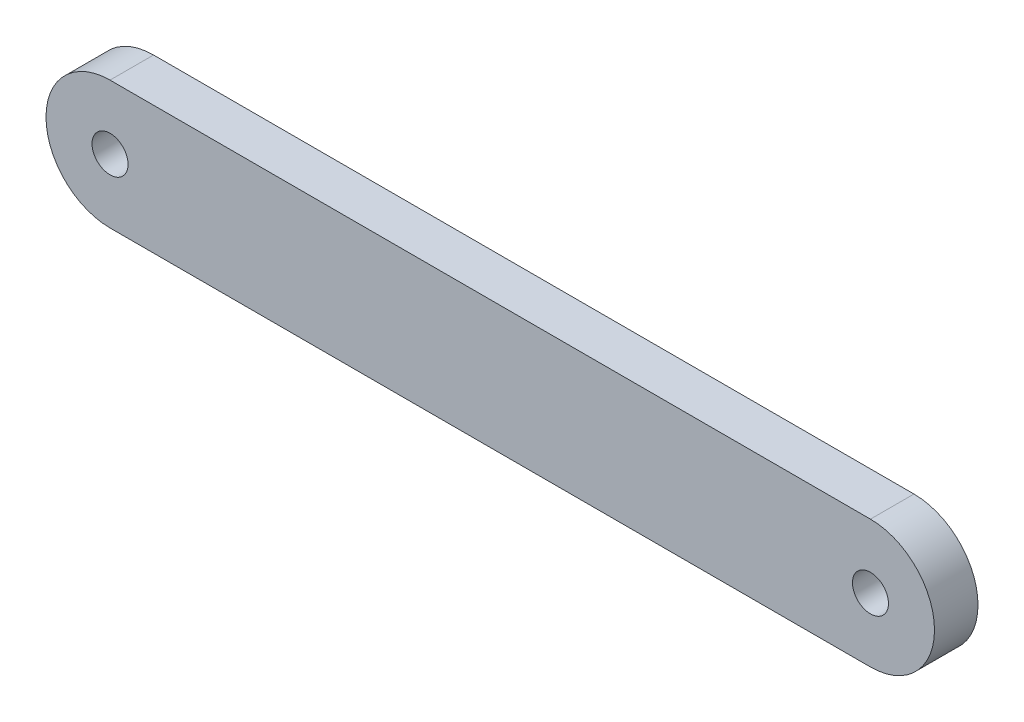
SolidWorks part; units mm, degrees
material "Acrylic (Medium-high impact)"
ref_plane "Front Plane" through (0, 0, 0) normal (0, 0, 1) x (1, 0, 0)
ref_plane "Top Plane" through (0, 0, 0) normal (0, 1, 0) x (1, 0, 0)
ref_plane "Right Plane" through (0, 0, 0) normal (1, 0, 0) x (0, 0, -1)
sketch "Sketch2" plane through (0, 0, 83.955) normal (0, 0, -1) x (-1, 0, 0)
  line L0 (-47.5, 0) -> (47.5, 0) construction
  line L1 (-47.5, 8) -> (47.5, 8)
  line L2 (-47.5, -8) -> (47.5, -8)
  line L3 (53.7502, -32.8621) -> (-53.7502, -32.8621) construction
  arc A0 (-47.5, 8) -> (-47.5, -8) centre (-47.5, 0) ccw
  arc A1 (47.5, -8) -> (47.5, 8) centre (47.5, 0) ccw
  circle A3 centre (-47.5, 0) radius 2.25
  circle A4 centre (47.5, 0) radius 2.25
  point P2 (0, 0)
  point P11 (0, 0)
  dimension "D2" = 4.5
  dimension "D3" = 8
  dimension "D1" = 95
extrude "Boss-Extrude1" add sketch "Sketch2" along normal blind 5.4356
